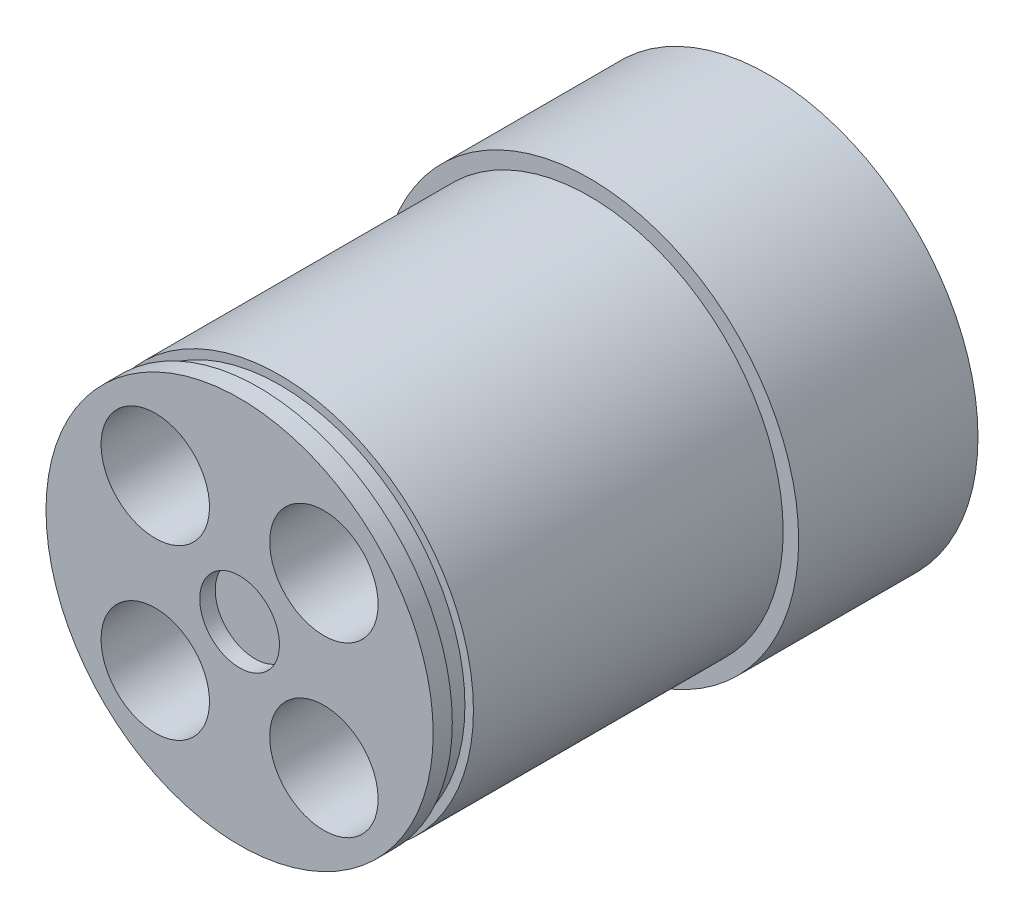
SolidWorks part; units mm, degrees
ref_plane "Front Plane" through (0, 0, 0) normal (0, 0, 1) x (1, 0, 0)
ref_plane "Top Plane" through (0, 0, 0) normal (0, 1, 0) x (1, 0, 0)
ref_plane "Right Plane" through (0, 0, 0) normal (1, 0, 0) x (0, 0, -1)
ref_axis "Z" through (0, 0, 24.309) along (0, 0, -1)
sketch "Sketch1" plane through (0, 0, 0) normal (0, 0, 1) x (1, 0, 0)
  circle A0 centre (0, 0) radius 12.5
  dimension "D1" = 25
extrude "Boss-Extrude1" add sketch "Sketch1" along normal blind 22.6
sketch "Sketch2" plane through (0, 0, 0) normal (0, 0, 1) x (1, 0, 0)
  circle A0 centre (0, 0) radius 13.5
  dimension "D1" = 27
extrude "Boss-Extrude2" add sketch "Sketch2" against normal blind 11.58
sketch "Sketch9" plane through (0, 0, 0) normal (1, 0, 0) x (0, 0, -1)
  line L0 (0, 0) -> (-20, 0) construction
  line L1 (-20, 0) -> (-20, -12.5) construction
  line L2 (-20, -12.5) -> (-21.365, -12.5)
  line L3 (-21.365, -12.5) -> (-21.365, -11.95)
  line L4 (-21.365, -11.95) -> (-20, -11.95)
  line L5 (-20, -11.95) -> (-20, -12.5)
  dimension "D1" = 20
  dimension "D2" = 25
  dimension "D3" = 1.365
  dimension "D4" = 23.9
revolve "Cut-Revolve1" cut sketch "Sketch9" angle 360 about axis through (0, 0, 24.309) along (0, 0, -1)
sketch "Sketch4" plane through (0, 0, 22.6) normal (0, 0, 1) x (1, 0, 0)
  circle A0 centre (0, 0) radius 2.575
  dimension "D1" = 5.15
extrude "MagnetSlot" cut sketch "Sketch4" against normal blind 1
sketch "Sketch6" plane through (0, 0, 22.6) normal (0, 0, 1) x (1, 0, 0)
  line L0 (0, 0) -> (5.4447, 5.4447) construction
  line L1 (0, 0) -> (0, 18.4845) construction
  line L2 (6.2068, 8.2889) -> (3.3627, 7.5268)
  line L3 (3.3627, 7.5268) -> (2.6006, 4.6826)
  line L4 (2.6006, 4.6826) -> (4.6826, 2.6006)
  line L5 (4.6826, 2.6006) -> (7.5268, 3.3627)
  line L6 (7.5268, 3.3627) -> (8.2889, 6.2068)
  line L7 (8.2889, 6.2068) -> (6.2068, 8.2889)
  circle A0 centre (5.4447, 5.4447) radius 2.55 construction
  dimension "D1" = 7.7
  dimension "D2" = 5.1
  dimension "D3" = 45
extrude "NutCut" cut sketch "Sketch6" against normal offset from surface (30.18 mm away) 4 up to face at (13.5, 0, -11.58)
sketch "Sketch7" plane through (0, 0, 22.6) normal (0, 0, 1) x (1, 0, 0)
  circle A0 centre (5.4447, 5.4447) radius 3.5
  dimension "D1" = 7
extrude "NutHole" cut sketch "Sketch7" against normal blind 15
sketch "Sketch8" plane through (0, 0, 22.6) normal (0, 0, 1) x (1, 0, 0)
  circle A0 centre (5.4447, 5.4447) radius 1.35
  dimension "D1" = 2.7
extrude "ScrewHole" cut sketch "Sketch8" against normal through all both and the other way through all
pattern_circular "CirPattern1" count 4 over 360 about axis through (0, 0, 24.309) along (0, 0, -1) of "MagnetSlot", "NutCut", "NutHole", "ScrewHole"
equation "\"BearingBaseDistance\"= 12"
equation "\"BearingOD\"= 32"
equation "\"BearingHeight\"= 4"
equation "\"SeatsOD\"= \"BearingOD\" + 10"
equation "\"WireHarnessHeight\"= 0.05in * 4 + 4.5"
equation "\"OuterWallWidth\"= 6"
equation "\"OverallOD\" = 50"
equation "\"RetainingRingThickness\" = 1.30"
equation "\"RetaininRingGrooveDiameter\" = 23.9"
equation "\"ShaftLengthAfterFlange\" = 2*\"BearingHeight\" + \"BearingBaseDistance\" + \"RetainingRingThickness\"*2\t'give a retaining ring thickness of extra clearance"
equation "\"RetainingRingGrooveBase\" = \"ShaftLengthAfterFlange\" - \"RetainingRingThickness\"*2"
equation "\"BearingID\" = 25"
equation "\"CoverClearance\" = 1"
equation "\"CoverThickness\" = 1"
equation "\"FlangHeight\" = \"CoverThickness\" + \"CoverClearance\" + \"WireHarnessHeight\""
equation "\"D1@Sketch1\"=\"BearingID\""
equation "\"D2@Sketch9\"=\"BearingID\""
equation "\"D3@Sketch9\"=\"RetainingRingThickness\"*1.05"
equation "\"D4@Sketch9\"=\"RetaininRingGrooveDiameter\""
equation "\"D1@Boss-Extrude2\"=\"FlangHeight\""
equation "\"D1@Sketch9\"=\"RetainingRingGrooveBase\""
equation "\"D1@Boss-Extrude1\"=\"ShaftLengthAfterFlange\""
